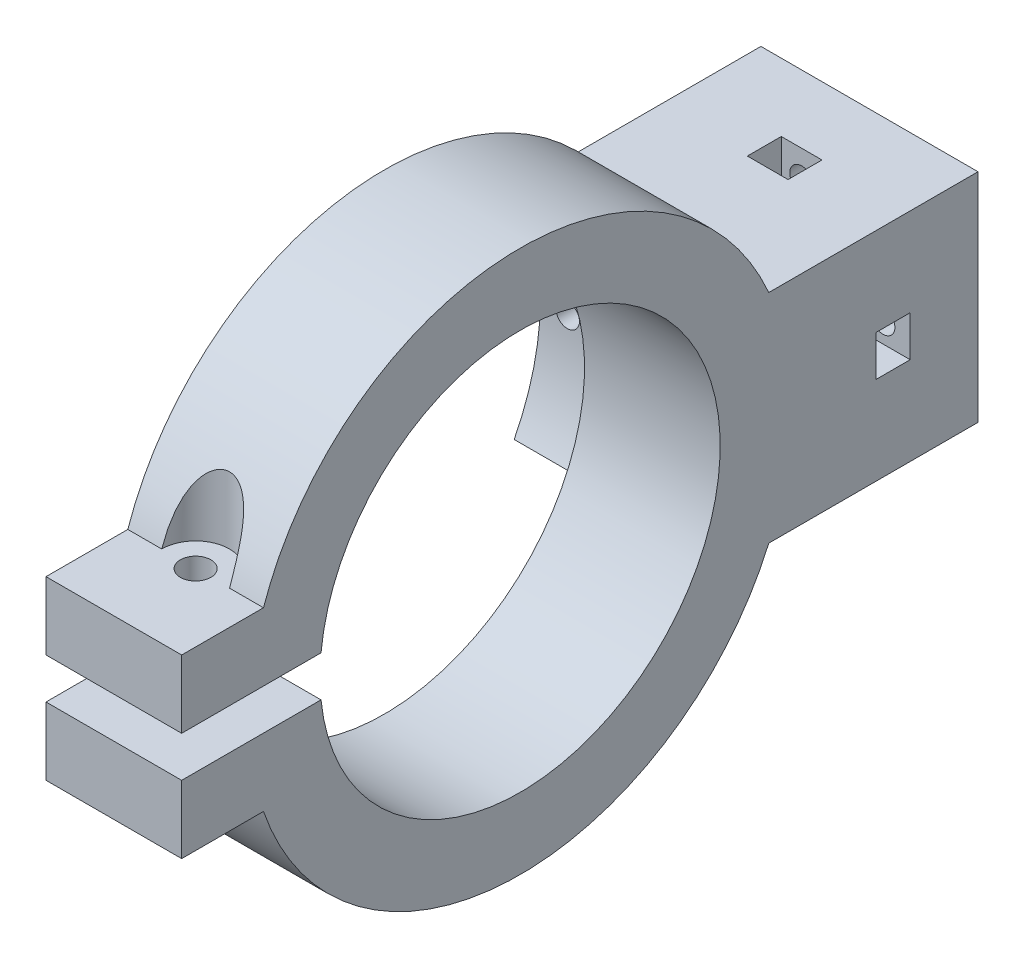
SolidWorks part; units mm, degrees
ref_plane "Front Plane" through (0, 0, 0) normal (0, 0, 1) x (1, 0, 0)
ref_plane "Top Plane" through (0, 0, 0) normal (0, 1, 0) x (1, 0, 0)
ref_plane "Right Plane" through (0, 0, 0) normal (1, 0, 0) x (0, 0, -1)
sketch "Sketch1" plane through (0, 0, 0) normal (1, 0, 0) x (0, -1, 0)
  line L1 (-16, 0) -> (16, 0)
  line L2 (-16, 0) -> (-16, 25)
  line L3 (-16, 25) -> (16, 25)
  line L4 (16, 0) -> (16, 25)
  circle A0 centre (0, 0) radius 4.5
  circle A1 centre (0, 0) radius 16
  dimension "D1" = 9
  dimension "D2" = 32
  dimension "D3" = 25
extrude "Boss-Extrude1" add sketch "Sketch1" along normal blind 32 contours A1 L4 L3 L2 | L1 A1 A0 | L1 A1 A0 region at (0, 0, -7.2098) region at (0, 0, 7.2098) region at (0, 0, -18.2703)
sketch "Sketch4" plane through (0, 0, 0) normal (-1, 0, 0) x (0, 0, 1)
  circle A0 centre (0, 0) radius 16
  dimension "D1" = 32
extrude "Cut-Extrude3" cut sketch "Sketch4" against normal blind 15
sketch "Sketch5" plane through (15, 0, 0) normal (-1, 0, 0) x (0, 0, 1)
  circle A0 centre (0, 0) radius 7
  circle A1 centre (0, 0) radius 4
  dimension "D1" = 8
  dimension "D2" = 14
extrude "Boss-Extrude2" add sketch "Sketch5" against normal up to surface (17 mm away) up to face at (32, 0, -8.5)
sketch "Sketch15" plane through (0, 0, 0) normal (-1, 0, 0) x (0, 0, 1)
  line L0 (0, -16) -> (-25, -16) construction
  line L1 (0, 16) -> (-16, 16)
  line L2 (0, 16) -> (0, -16)
  line L3 (0, -16) -> (-16, -16)
  line L4 (-16, 16) -> (-16, -16)
  arc A0 (0, 16) -> (0, -16) centre (0, 0) ccw construction
extrude "Cut-Extrude6" cut sketch "Sketch15" against normal up to surface (15 mm away) up to face at (15, 0, 0)
sketch "Sketch16" plane through (0, 0, -25) normal (0, 0, -1) x (-1, 0, 0)
  line L4 (0, -16) -> (0, 16)
  line L5 (0, 16) -> (-32, 16)
  line L6 (-32, 16) -> (-32, -16)
  line L7 (-32, -16) -> (0, -16)
  line L8 (0, -16) -> (0, 16)
  line L9 (0, 16) -> (-32, 16)
  line L10 (-32, 16) -> (-32, -16)
  line L11 (-32, -16) -> (0, -16)
  dimension "D1" = 0
extrude "Boss-Extrude6" add sketch "Sketch16" along normal blind 30
sketch "Sketch17" plane through (0, 0, -16) normal (0, 0, 1) x (1, 0, 0)
  line L0 (0, 16) -> (0, -16) construction
  line L1 (15, -16) -> (0, -16) construction
  line L2 (32, -16) -> (32, 16) construction
  line L3 (15, 16) -> (0, 16) construction
  line L4 (32, 16) -> (15, 16) construction
  circle A0 centre (4, 0) radius 1.75
  circle A1 centre (16, 12) radius 1.75
  circle A2 centre (28, 0) radius 1.75
  circle A3 centre (16, -12) radius 1.75
  dimension "D1" = 3.5
  dimension "D2" = 4
  dimension "D3" = 16
  dimension "D4" = 16
  dimension "D5" = 3.5
  dimension "D6" = 4
  dimension "D7" = 3.5
  dimension "D8" = 24
  dimension "D9" = 16
  dimension "D10" = 24
  dimension "D11" = 12
  dimension "D12" = 3.5
extrude "Cut-Extrude8" cut sketch "Sketch17" against normal through all
sketch "Sketch19" plane through (0, 0, -55) normal (0, 0, -1) x (-1, 0, 0)
  line L7 (0, 3) -> (-5.7321, 3)
  line L8 (-5.7321, 3) -> (-7.4641, 0)
  line L9 (-7.4641, 0) -> (-5.7321, -3)
  line L10 (-5.7321, -3) -> (0, -3)
  line L13 (-16, -8.5359) -> (-19, -10.2679)
  line L14 (-19, -10.2679) -> (-19, -16)
  line L17 (-13, -16) -> (-13, -10.2679)
  line L18 (-13, -10.2679) -> (-16, -8.5359)
  line L19 (-24.5359, 0) -> (-26.2679, 3)
  line L20 (-26.2679, 3) -> (-32, 3)
  line L23 (-32, -3) -> (-26.2679, -3)
  line L24 (-26.2679, -3) -> (-24.5359, 0)
  line L25 (0, -16) -> (0, 16) construction
  line L28 (-16, 8.5359) -> (-13, 10.2679)
  line L29 (-13, 10.2679) -> (-13, 16)
  line L31 (-32, -16) -> (0, -16)
  line L32 (0, -16) -> (0, 16)
  line L33 (0, 16) -> (-32, 16)
  line L34 (-32, 16) -> (-32, -16)
  line L35 (-19, -16) -> (-13, -16)
  line L36 (0, -3) -> (0, 3)
  line L37 (-13, 16) -> (-19, 16)
  line L38 (-32, 3) -> (-32, -3)
  line L40 (-19, 16) -> (-19, 10.2679)
  line L41 (-30.5981, 1.5) -> (-31.3919, 0.125) [skipped]
  line L42 (-30.5981, -1.5) -> (-29.8042, -2.875) [skipped]
  line L43 (-0.8815, 0.5986) -> (-1.6754, 1.9736) [skipped]
  line L44 (-1.9223, -2.4014) -> (-1.1285, -1.0264) [skipped]
  line L45 (-18.1495, -14.2231) -> (-16.7745, -15.0169) [skipped]
  line L46 (-13.8505, -14.2231) -> (-12.4755, -13.4292) [skipped]
  line L47 (-19, 10.2679) -> (-16, 8.5359)
  line L48 (-16.5986, 15.1185) -> (-17.9736, 14.3246) [skipped]
  line L49 (-13.5986, 14.0777) -> (-14.9736, 14.8715) [skipped]
  arc A0 (-19, 12) -> (-13, 12) centre (-16, 12) ccw construction
  arc A1 (-4, 3) -> (-4, -3) centre (-4, 0) ccw construction
  arc A2 (-13, -12) -> (-19, -12) centre (-16, -12) ccw construction
  arc A3 (-28, -3) -> (-28, 3) centre (-28, 0) ccw construction
  dimension "D1" = 6
  dimension "D2" = 6
  dimension "D3" = 6
  dimension "D4" = 6
  dimension "D5" = 0
extrude "Cut-Extrude10" cut sketch "Sketch19" against normal blind 5 from offset 10 offset against normal yes
sketch "Sketch20" plane through (0, 0, -55) normal (0, 0, -1) x (-1, 0, 0)
  line L0 (-28, 0) -> (-16, 0) construction
  line L1 (-16, 0) -> (-16, 12) construction
  circle A0 centre (-16, 0) radius 4.25
  dimension "D1" = 8.5
extrude "Cut-Extrude11" cut sketch "Sketch20" against normal up to surface (39 mm away) up to face at (5.75, 0, -16)
sketch "Sketch21" plane through (15, 0, 0) normal (-1, 0, 0) x (0, 0, 1)
  line L9 (0, 16) -> (-16, 16)
  line L10 (-16, 16) -> (-16, 13.4361)
  line L11 (-16, 13.4361) -> (-16, 10.5639)
  line L12 (-16, 10.5639) -> (-16, 4.1307)
  line L13 (-16, 4.1307) -> (-16, -4.1307)
  line L14 (-16, -4.1307) -> (-16, -10.5639)
  line L15 (-16, -10.5639) -> (-16, -13.4361)
  line L16 (-16, -13.4361) -> (-16, -16)
  line L17 (-16, -16) -> (0, -16)
  line L18 (0, 16) -> (-16, 16)
  line L19 (-16, 16) -> (-16, 13.4361)
  line L20 (-16, 13.4361) -> (-16, 10.5639)
  line L21 (-16, 10.5639) -> (-16, 4.1307)
  line L22 (-16, 4.1307) -> (-16, -4.1307)
  line L23 (-16, -4.1307) -> (-16, -10.5639)
  line L24 (-16, -10.5639) -> (-16, -13.4361)
  line L25 (-16, -13.4361) -> (-16, -16)
  line L26 (-16, -16) -> (0, -16)
  arc A1 (0, -16) -> (0, 16) centre (0, 0) ccw
  arc A2 (0, -16) -> (0, 16) centre (0, 0) ccw
  dimension "D1" = 0
extrude "Cut-Extrude12" cut sketch "Sketch21" against normal blind 10
sketch "Sketch22" plane through (25, 0, 0) normal (-1, 0, 0) x (0, 0, 1)
  circle A0 centre (0, 0) radius 6.5
  dimension "D1" = 13
extrude "Cut-Extrude13" cut sketch "Sketch22" against normal blind 10
sketch "Sketch23" plane through (25, 0, 0) normal (-1, 0, 0) x (0, 0, 1)
  line L0 (0, 0) -> (0, 12.5) construction
  line L1 (0, 0) -> (0, -12.5) construction
  circle A0 centre (0, 12.5) radius 1.75
  circle A1 centre (0, -12.5) radius 1.75
  dimension "D3" = 3.5
  dimension "D4" = 3.5
  dimension "D1" = 12.5
  dimension "D2" = 12.5
extrude "Cut-Extrude14" cut sketch "Sketch23" against normal blind 10
sketch "Sketch24" plane through (25, 0, 0) normal (-1, 0, 0) x (0, 0, 1)
  circle A0 centre (0, 0) radius 22.5
  dimension "D1" = 45
extrude "Cut-Extrude16" cut sketch "Sketch24" along normal up to surface (25 mm away) up to face at (0, 0, -35.5)
sketch "Sketch25" plane through (0, 0, -55) normal (0, 0, -1) x (-1, 0, 0)
  circle A0 centre (-16, 0) radius 4.25 construction
  circle A1 centre (-16, 0) radius 4.25
extrude "Boss-Extrude7" add sketch "Sketch25" against normal up to surface (7.5 mm away) from offset 25 up to face at (14.3423, 12.561, -18.6674) offset against normal yes
sketch "Sketch26" plane through (25, 0, 0) normal (-1, 0, 0) x (0, 0, 1)
  circle A0 centre (0, 0) radius 8.5
  dimension "D1" = 17
extrude "Cut-Extrude17" cut sketch "Sketch26" against normal blind 10
sketch "Sketch27" plane through (25, 0, 0) normal (-1, 0, 0) x (0, 0, 1)
  circle A0 centre (0, 0) radius 16
extrude "Boss-Extrude8" add sketch "Sketch27" against normal blind 7
sketch "Sketch28" plane through (25, 0, 0) normal (-1, 0, 0) x (0, 0, 1)
  line L0 (-22.5, 0) -> (12.5, 0) construction
  circle A0 centre (12.5, 0) radius 35
  arc A2 (-16, 15.8193) -> (-16, -15.8193) centre (0, 0) ccw construction
  dimension "D1" = 70
  dimension "D2" = 35
extrude "Cut-Extrude18" cut sketch "Sketch28" along normal through all
sketch "Sketch29" plane through (25, 0, 0) normal (-1, 0, 0) x (0, 0, 1)
  circle A0 centre (12.5, 0) radius 35
  dimension "D1" = 70
extrude "Boss-Extrude9" add sketch "Sketch29" against normal blind 7
sketch "Sketch30" plane through (25, 0, 0) normal (-1, 0, 0) x (0, 0, 1)
  arc A2 (-18.6288, -16) -> (-18.6288, 16) centre (12.5, 0) ccw
  arc A3 (-18.6288, 16) -> (-18.6288, -16) centre (12.5, 0) ccw
  arc A4 (-18.6288, -16) -> (-18.6288, 16) centre (12.5, 0) ccw
  arc A5 (-18.6288, 16) -> (-18.6288, -16) centre (12.5, 0) ccw
  dimension "D1" = 0
extrude "Boss-Extrude10" add sketch "Sketch30" along normal blind 3
sketch "Sketch31" plane through (22, 0, 0) normal (-1, 0, 0) x (0, 0, 1)
  circle A0 centre (12.5, 0) radius 15
  dimension "D1" = 30
extrude "Cut-Extrude19" cut sketch "Sketch31" against normal through all
sketch "Sketch32" plane through (22, 0, 0) normal (-1, 0, 0) x (0, 0, 1)
  circle A0 centre (12.5233, 25.4) radius 2.2
  circle A1 centre (-5.444, 17.977) radius 2.2
  circle A2 centre (-12.9, 0.0233) radius 2.2
  circle A3 centre (-5.477, -17.944) radius 2.2
  circle A4 centre (12.4767, -25.4) radius 2.2
  circle A5 centre (30.444, -17.977) radius 2.2
  circle A6 centre (30.477, 17.944) radius 2.2
  dimension "D1" = 4.4
  dimension "D2" = 4.4
  dimension "D3" = 4.4
  dimension "D4" = 4.4
  dimension "D5" = 4.4
  dimension "D6" = 4.4
  dimension "D7" = 4.4
extrude "Cut-Extrude20" cut sketch "Sketch32" against normal through all
sketch "Sketch33" plane through (22, 0, 0) normal (-1, 0, 0) x (0, 0, 1)
  circle A0 centre (12.5, 0) radius 40
  circle A1 centre (12.5, 0) radius 29.5
  dimension "D1" = 80
  dimension "D2" = 59
extrude "Boss-Extrude11" add sketch "Sketch33" along normal blind 10 and the other way blind 10
sketch "Sketch34" plane through (22, 0, 0) normal (-1, 0, 0) x (0, 0, 1)
  circle A1 centre (12.5, 0) radius 29.5
  circle A2 centre (12.5, 0) radius 29.5
  dimension "D1" = 0
extrude "Cut-Extrude21" cut sketch "Sketch34" against normal blind 10
sketch "Sketch35" plane through (12, 0, 0) normal (-1, 0, 0) x (0, 0, 1)
  line L0 (12.5, 0) -> (75.1366, 0) construction
  line L2 (34.2927, 3) -> (60.4376, 3)
  line L3 (34.2927, 3) -> (34.2927, -3)
  line L4 (34.2927, -3) -> (60.4376, -3)
  line L5 (60.4376, 3) -> (60.4376, -3)
  dimension "D1" = 3
  dimension "D2" = 3
extrude "Cut-Extrude22" cut sketch "Sketch35" against normal through all
sketch "Sketch36" plane through (12, 0, 0) normal (-1, 0, 0) x (0, 0, 1)
  line L0 (52.3873, 3) -> (41.8471, 3) construction
  line L1 (48.4013, 3) -> (62.3873, 3)
  line L2 (48.4013, 3) -> (48.4013, 13)
  line L3 (48.4013, 13) -> (62.3873, 13)
  line L4 (62.3873, 3) -> (62.3873, 13)
  line L5 (0, 0) -> (67.177, 0) construction
  line L6 (48.4013, -13) -> (62.3873, -13)
  line L7 (62.3873, -3) -> (62.3873, -13)
  line L8 (48.4013, -3) -> (62.3873, -3)
  line L9 (48.4013, -3) -> (48.4013, -13)
  dimension "D1" = 10
  dimension "D2" = 10
extrude "Boss-Extrude12" add sketch "Sketch36" against normal blind 20
sketch "Sketch37" plane through (0, 13, 0) normal (0, 1, 0) x (1, 0, 0)
  line L0 (32, -50.3286) -> (12, -50.3286) construction
  circle A0 centre (22, -50.3286) radius 2.25
  dimension "D1" = 4.5
extrude "Cut-Extrude23" cut sketch "Sketch37" against normal through all and the other way through all
sketch "Sketch38" plane through (0, 13, 0) normal (0, 1, 0) x (1, 0, 0)
  circle A0 centre (22, -50.3286) radius 5
  dimension "D1" = 10
extrude "Cut-Extrude24" cut sketch "Sketch38" along normal through all
sketch "Sketch39" plane through (0, -13, 0) normal (0, -1, 0) x (1, 0, 0)
  line L1 (25.75, 52.4936) -> (22, 54.6587)
  line L2 (22, 54.6587) -> (18.25, 52.4936)
  line L3 (18.25, 52.4936) -> (18.25, 48.1635)
  line L4 (18.25, 48.1635) -> (22, 45.9984)
  line L5 (22, 45.9984) -> (25.75, 48.1635)
  line L6 (25.75, 48.1635) -> (25.75, 52.4936)
  line L8 (12, 50.3286) -> (12, -24.1606) construction
  circle A0 centre (22, 50.3286) radius 3.75 construction
  dimension "D1" = 7.5
extrude "Cut-Extrude25" cut sketch "Sketch39" along normal through all
